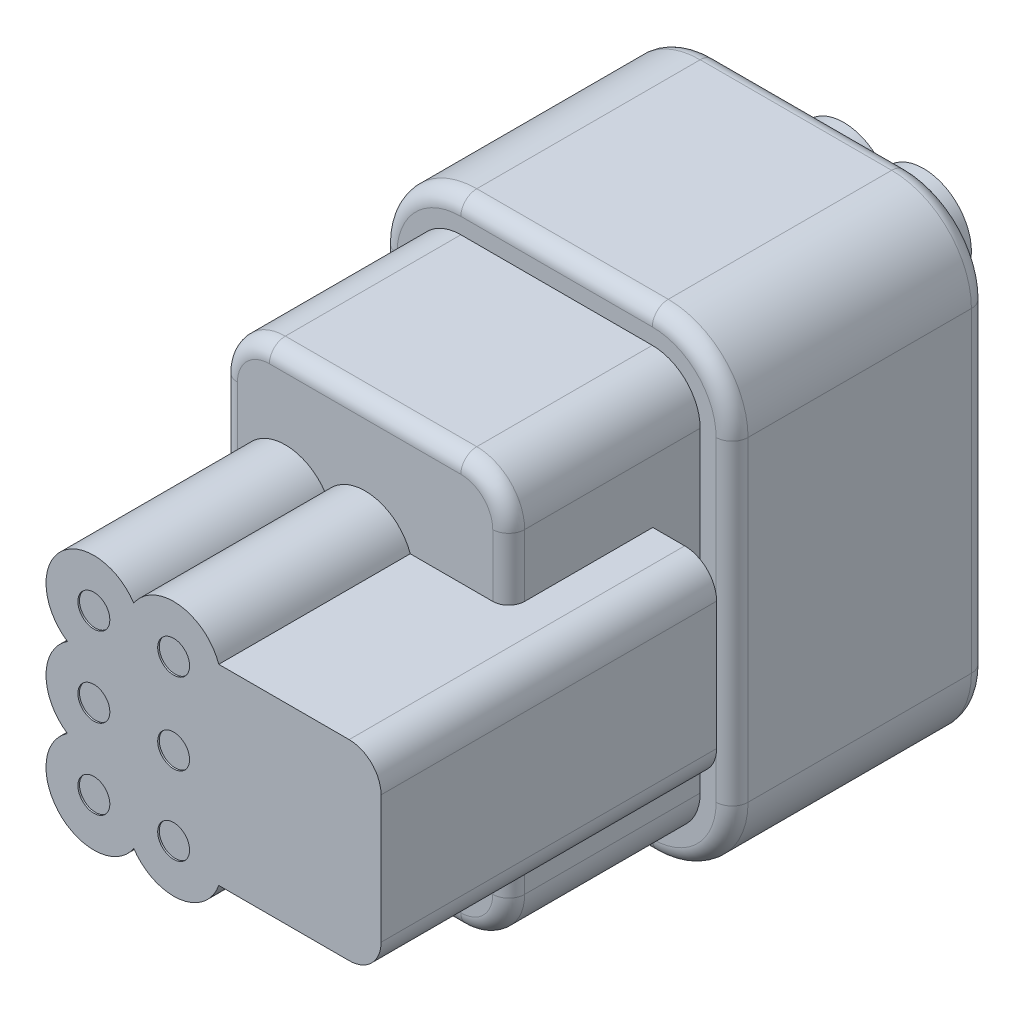
SolidWorks part; units mm, degrees
ref_plane "正面" through (0, 0, 0) normal (0, 0, 1) x (1, 0, 0)
ref_plane "平面" through (0, 0, 0) normal (0, 1, 0) x (1, 0, 0)
ref_plane "右側面" through (0, 0, 0) normal (1, 0, 0) x (0, 0, -1)
sketch "ｽｹｯﾁ1" plane through (0, 0, 0) normal (0, 0, 1) x (1, 0, 0)
  line L1 (5, 0) -> (17, 0)
  line L2 (0, 5) -> (0, 24.8)
  line L3 (5, 29.8) -> (17, 29.8)
  line L4 (22, 5) -> (22, 24.8)
  arc A0 (17, 29.8) -> (22, 24.8) centre (17, 24.8) cw
  arc A1 (17, 0) -> (22, 5) centre (17, 5) ccw
  arc A2 (5, 0) -> (0, 5) centre (5, 5) cw
  arc A3 (0, 24.8) -> (5, 29.8) centre (5, 24.8) cw
  point P7 (22, 29.8)
  point P12 (0, 0)
  point P15 (0, 29.8)
  dimension "D3" = 5
  dimension "D1" = 29.8
  dimension "D2" = 22
extrude "ﾎﾞｽ - 押し出し1" add sketch "ｽｹｯﾁ1" along normal blind 16
sketch "ｽｹｯﾁ2" plane through (0, 0, 16) normal (0, 0, 1) x (1, 0, 0)
  line L8 (17, 27.8) -> (5, 27.8)
  line L9 (2, 24.8) -> (2, 5)
  line L10 (5, 2) -> (17, 2)
  line L11 (20, 5) -> (20, 24.8)
  line L12 (17, 27.8) -> (5, 27.8)
  line L13 (2, 24.8) -> (2, 5)
  line L14 (5, 2) -> (17, 2)
  line L15 (20, 5) -> (20, 24.8)
  arc A8 (20, 24.8) -> (17, 27.8) centre (17, 24.8) ccw
  arc A9 (5, 27.8) -> (2, 24.8) centre (5, 24.8) ccw
  arc A10 (2, 5) -> (5, 2) centre (5, 5) ccw
  arc A11 (17, 2) -> (20, 5) centre (17, 5) ccw
  arc A12 (20, 24.8) -> (17, 27.8) centre (17, 24.8) ccw
  arc A13 (5, 27.8) -> (2, 24.8) centre (5, 24.8) ccw
  arc A14 (2, 5) -> (5, 2) centre (5, 5) ccw
  arc A15 (17, 2) -> (20, 5) centre (17, 5) ccw
  dimension "D1" = 2
extrude "ﾎﾞｽ - 押し出し2" add sketch "ｽｹｯﾁ2" along normal blind 12
sketch "ｽｹｯﾁ3" plane through (0, 0, 28) normal (0, 0, 1) x (1, 0, 0)
  line L2 (20, 5) -> (20, 24.8) construction
  arc A0 (4.3417, 12.4) -> (4.3417, 17.4) centre (6, 14.9) cw
  arc A1 (12.6583, 12.4) -> (12.6583, 17.4) centre (11, 14.9) ccw
  arc A3 (8.5, 8.2417) -> (4.3417, 12.4) centre (6, 9.9) cw
  arc A6 (8.5, 21.5583) -> (4.3417, 17.4) centre (6, 19.9) ccw
  arc A8 (8.5, 21.5583) -> (12.6583, 17.4) centre (11, 19.9) cw
  arc A11 (8.5, 8.2417) -> (12.6583, 12.4) centre (11, 9.9) ccw
  point P1 (14, 14.9)
  point P3 (14, 9.9)
  point P12 (11, 14.9)
  point P14 (11, 9.9)
  point P16 (6, 14.9)
  point P18 (6, 9.9)
  point P19 (9, 9.9)
  point P20 (11, 19.9)
  point P22 (6, 19.9)
  point P23 (14, 19.9)
  point P24 (11, 17.4)
  point P26 (20, 14.9)
  point P27 (13.3908, 19.1691)
  point P31 (13.3908, 10.6309)
  point P34 (3.6092, 19.1691)
  point P36 (9, 19.9)
  point P37 (3.6092, 10.6309)
  point P41 (13.3908, 15.6309)
  point P44 (9, 14.9)
  point P47 (3.6092, 15.6309)
extrude "ﾎﾞｽ - 押し出し3" add sketch "ｽｹｯﾁ3" along normal blind 12 and the other way blind 35
fillet "ﾌｨﾚｯﾄ1" radius 1 24 edges at (11, 0, 0) (1.4645, 1.4645, 0) (0, 14.9, 0) (1.4645, 28.3355, 0) (11, 29.8, 0) (20.5355, 28.3355, 0) (22, 14.9, 0) (20.5355, 1.4645, 0) (2.8787, 2.8787, 28) (2, 14.9, 28) (2.8787, 26.9213, 28) (11, 27.8, 28) (19.1213, 26.9213, 28) (20, 14.9, 28) (19.1213, 2.8787, 28) (1.4645, 1.4645, 16) (0, 14.9, 16) (1.4645, 28.3355, 16) (11, 29.8, 16) (20.5355, 28.3355, 16) (22, 14.9, 16) (20.5355, 1.4645, 16) (11, 2, 28) (11, 0, 16)
sketch "ｽｹｯﾁ4" plane through (20, 0, 0) normal (1, 0, 0) x (0, 0, -1)
  line L0 (-16, 14.9) -> (-27, 14.9) construction
  line L1 (-16, 5) -> (-16, 24.8) construction
  line L2 (-27, 24.8) -> (-27, 5) construction
  line L3 (-27, 20.9) -> (-40, 20.9)
  line L4 (-27, 20.9) -> (-18.9708, 20.9)
  line L5 (-18.9708, 20.9) -> (-18.9708, 8.9)
  line L6 (-40, 22.9) -> (-40, 17.4) construction
  line L7 (-40, 20.9) -> (-40, 8.9)
  line L8 (-40, 17.4) -> (-40, 12.4) construction
  line L9 (-27, 8.9) -> (-18.9708, 8.9)
  line L10 (-27, 8.9) -> (-40, 8.9)
  point P16 (-18.9708, 14.9)
  point P18 (-40, 14.9)
  dimension "D1" = 6
extrude "ﾎﾞｽ - 押し出し4" add sketch "ｽｹｯﾁ4" along normal blind 4 and the other way blind 12
fillet "ﾌｨﾚｯﾄ2" radius 2 2 edges at (24, 20.9, 29.4854) (24, 8.9, 29.4854)
sketch "ｽｹｯﾁ5" plane through (0, 0, -7) normal (0, 0, -1) x (-1, 0, 0)
  circle A0 centre (-11, 19.9) radius 1.5
  circle A1 centre (-11, 14.9) radius 1.5
  circle A2 centre (-11, 9.9) radius 1.5
  circle A3 centre (-6, 19.9) radius 1.5
  circle A4 centre (-6, 14.9) radius 1.5
  circle A5 centre (-6, 9.9) radius 1.5
  dimension "D1" = 3
extrude "ｶｯﾄ - 押し出し1" cut sketch "ｽｹｯﾁ5" against normal blind 0.1
sketch "ｽｹｯﾁ6" plane through (0, 0, 40) normal (0, 0, 1) x (1, 0, 0)
  circle A0 centre (11, 19.9) radius 1
  circle A1 centre (11, 14.8111) radius 1
  circle A2 centre (11, 9.9) radius 1
  circle A3 centre (6, 19.9) radius 1
  circle A4 centre (6, 14.9) radius 1
  circle A5 centre (6, 9.9) radius 1
  arc A6 (8.5, 21.5583) -> (4.3417, 17.4) centre (6, 19.9) ccw construction
  arc A7 (4.3417, 17.4) -> (4.3417, 12.4) centre (6, 14.9) ccw construction
  arc A8 (4.3417, 12.4) -> (8.5, 8.2417) centre (6, 9.9) ccw construction
  arc A9 (13.8284, 20.9) -> (8.5, 21.5583) centre (11, 19.9) ccw construction
  arc A10 (8.5, 8.2417) -> (13.8284, 8.9) centre (11, 9.9) ccw construction
  point P8 (0, 0)
  point P28 (0, 0)
  dimension "D1" = 2
extrude "ｶｯﾄ - 押し出し2" cut sketch "ｽｹｯﾁ6" against normal blind 0.1
